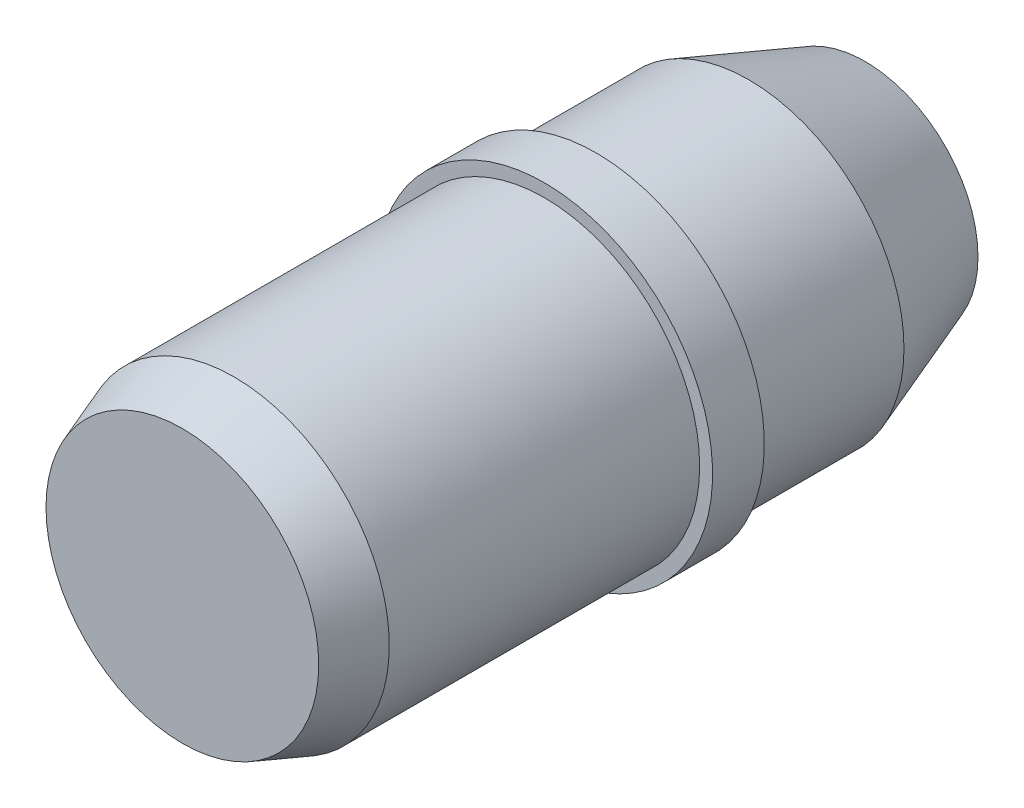
SolidWorks part; units mm, degrees
ref_plane "Front Plane" through (0, 0, 0) normal (0, 0, 1) x (1, 0, 0)
ref_plane "Top Plane" through (0, 0, 0) normal (0, 1, 0) x (1, 0, 0)
ref_plane "Right Plane" through (0, 0, 0) normal (1, 0, 0) x (0, 0, -1)
sketch "Sketch1" plane through (0, 0, 0) normal (0, 0, 1) x (1, 0, 0)
  circle A0 centre (0, 0) radius 3
  dimension "D1" = 6
extrude "Boss-Extrude1" add sketch "Sketch1" along normal blind 7
chamfer "Chamfer1" distance 1 angle 20 1 edges at (3, 0, 7) first distance on face at (3, 0, 7)
sketch "Sketch2" plane through (0, 0, 0) normal (0, 0, -1) x (-1, 0, 0)
  circle A0 centre (0, 0) radius 3.25
  dimension "D1" = 6.5
extrude "Boss-Extrude3" add sketch "Sketch2" along normal blind 1
sketch "Sketch4" plane through (0, 0, -1) normal (0, 0, -1) x (-1, 0, 0)
  circle A0 centre (0, 0) radius 3
  dimension "D1" = 6
extrude "Boss-Extrude4" add sketch "Sketch4" along normal blind 5.2
chamfer "Chamfer2" distance 2.25 angle 20 1 edges at (-3, 0, -6.2) first distance on face at (-3, 0, -6.2)
extrude "Boss-Extrude5" add sketch "Sketch2<2>" along normal blind 1
sketch "Sketch2<2>" plane through (0, 0, 0) normal (0, 0, -1) x (-1, 0, 0) same geometry as "Sketch2"
